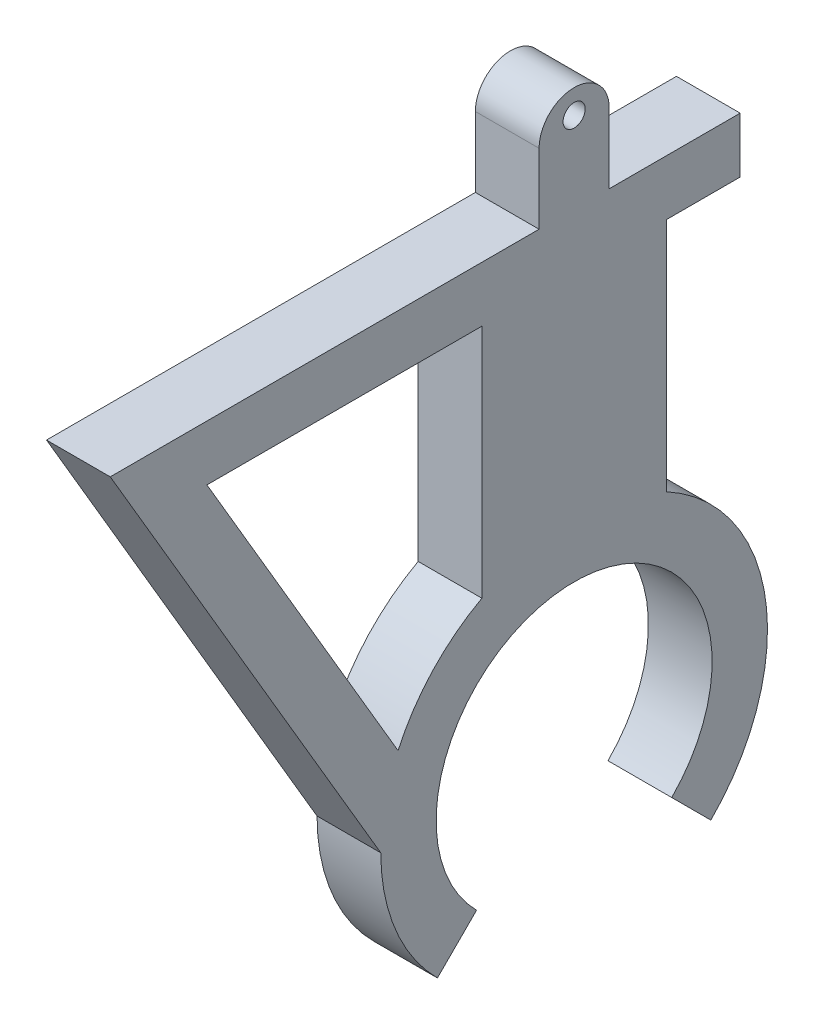
SolidWorks part; units mm, degrees
ref_plane "Front Plane" through (0, 0, 0) normal (0, 0, 1) x (1, 0, 0)
ref_plane "Top Plane" through (0, 0, 0) normal (0, 1, 0) x (1, 0, 0)
ref_plane "Right Plane" through (0, 0, 0) normal (1, 0, 0) x (0, 0, -1)
sketch "Sketch1" plane through (0, 0, 0) normal (1, 0, 0) x (0, 0, -1)
  line L0 (-2.6446, -2.6446) -> (2.6446, -2.6446) construction
  line L1 (-2.6446, -2.6446) -> (-3.7052, -3.7052)
  line L2 (3.7052, -3.7052) -> (2.6446, -2.6446)
  line L3 (0, 0) -> (0, 6.3411) construction
  line L4 (-2.5, 12.4907) -> (-0.95, 12.4907)
  line L5 (-2.5, 12.4907) -> (-2.5, 4.6052)
  line L6 (-0.95, 14.3907) -> (-0.95, 12.4907)
  line L7 (2.5, 12.4907) -> (2.5, 4.6052)
  line L8 (-2.5, 12.4907) -> (2.5, 4.6052) construction
  line L9 (-2.5, 4.6052) -> (2.5, 12.4907) construction
  line L10 (-0.95, 14.3907) -> (0.95, 14.3907) construction
  line L11 (0.95, 12.4907) -> (2.5, 12.4907)
  line L12 (0.95, 14.3907) -> (0.95, 12.4907)
  line L13 (-0.95, 14.3907) -> (0.95, 12.4907) construction
  line L14 (-0.95, 12.4907) -> (0.95, 14.3907) construction
  line L15 (-2.5, 12.4907) -> (-12.5716, 12.4907)
  line L16 (-12.5716, 12.4907) -> (-5.24, 0)
  line L17 (-2.5, 10.9907) -> (-9.9519, 10.9907)
  line L18 (-9.9519, 10.9907) -> (-4.7717, 2.1653)
  line L19 (-9.9519, 10.9907) -> (-3.9464, 0.7593) construction
  line L21 (2.5, 12.4907) -> (4.5, 12.4907)
  line L22 (2.5, 12.4907) -> (2.5, 10.9907)
  line L23 (2.5, 10.9907) -> (4.5, 10.9907)
  line L24 (4.5, 12.4907) -> (4.5, 10.9907)
  arc A0 (-2.6446, -2.6446) -> (2.6446, -2.6446) centre (0, 0) cw
  arc A1 (-3.7052, -3.7052) -> (-2.5, 4.6052) centre (0, 0) cw
  arc A2 (2.5, 4.6052) -> (3.7052, -3.7052) centre (0, 0) cw
  arc A3 (-3.7052, -3.7052) -> (3.7052, -3.7052) centre (0, 0) cw construction
  arc A4 (-0.95, 14.3907) -> (0.95, 14.3907) centre (0, 14.3907) cw
  circle A5 centre (0, 14.6907) radius 0.3
  point P7 (0, 8.5479)
  point P12 (0, 3.74)
  point P16 (0, 14.3907)
  point P17 (0, 13.4407)
  dimension "D1" = 3.74
  dimension "D3" = 1.5
  dimension "D6" = 1.9
  dimension "D8" = 0.6
  dimension "D9" = 1.5
  dimension "D2" = 90
  dimension "D4" = 7.8855
  dimension "D5" = 5
  dimension "D7" = 1.9
  dimension "D10" = 2
extrude "Boss-Extrude1" add sketch "Sketch1" along normal blind 1.7272 contours A4 L6 L4 L5 A1 L1 A0 L2 A2 L7 L11 L12 A5 | L16 A1 L18 L17 L5 L15 | L24 L21 L7 L23 region at (0, 5.8984, 0) region at (0, 6.3266, 8.7674) region at (0, 11.7407, -3.5)
